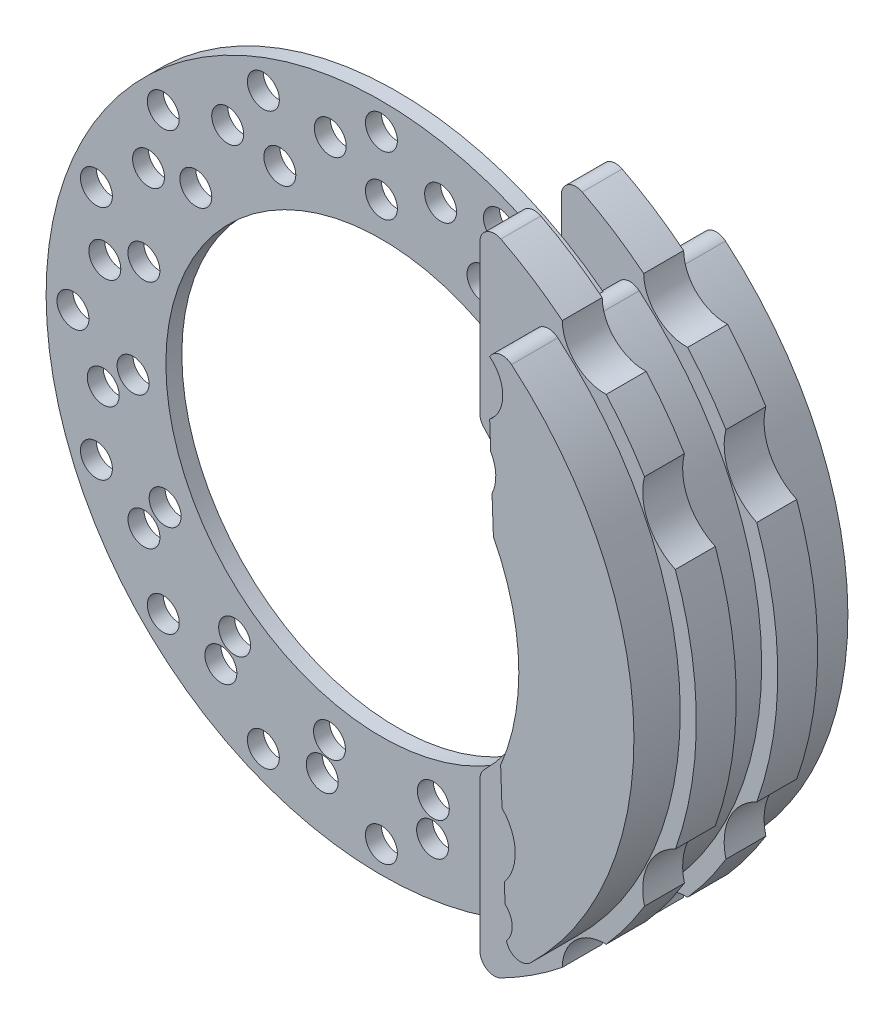
SolidWorks part; units mm, degrees
ref_plane "Front Plane" through (0, 0, 0) normal (0, 0, 1) x (1, 0, 0)
ref_plane "Top Plane" through (0, 0, 0) normal (0, 1, 0) x (1, 0, 0)
ref_plane "Right Plane" through (0, 0, 0) normal (1, 0, 0) x (0, 0, -1)
sketch "Sketch2" plane through (0, 0, 0) normal (0, 0, 1) x (1, 0, 0)
  circle A0 centre (0, 0) radius 210
  circle A1 centre (0, 0) radius 135
  dimension "D1" = 420
  dimension "D2" = 270
extrude "Boss-Extrude1" add sketch "Sketch2" along normal blind 10
sketch "Sketch3" plane through (0, 0, 0) normal (0, 0, 1) x (1, 0, 0)
  circle A0 centre (0, 0) radius 156.4104 construction
  circle A1 centre (0, 0) radius 177.149 construction
  circle A2 centre (0, 0) radius 193.1972 construction
  circle A3 centre (0, 193.1972) radius 10
  circle A17 centre (37.0719, 173.2265) radius 10
  circle A18 centre (100.5409, 145.8537) radius 10
  circle A19 centre (148.7034, 96.2759) radius 10
  circle A20 centre (174.2272, 32.041) radius 10
  circle A21 centre (173.2265, -37.0719) radius 10
  circle A22 centre (145.8537, -100.5409) radius 10
  circle A23 centre (96.2759, -148.7034) radius 10
  circle A24 centre (32.041, -174.2272) radius 10
  circle A25 centre (-37.0719, -173.2265) radius 10
  circle A26 centre (-100.5409, -145.8537) radius 10
  circle A27 centre (-148.7034, -96.2759) radius 10
  circle A28 centre (-174.2272, -32.041) radius 10
  circle A29 centre (-173.2265, 37.0719) radius 10
  circle A30 centre (-145.8537, 100.5409) radius 10
  circle A31 centre (-96.2759, 148.7034) radius 10
  circle A32 centre (-32.041, 174.2272) radius 10
  circle A33 centre (73.9334, 178.4909) radius 10
  circle A34 centre (136.611, 136.611) radius 10
  circle A35 centre (178.4909, 73.9334) radius 10
  circle A36 centre (193.1972, 0) radius 10
  circle A37 centre (178.4909, -73.9334) radius 10
  circle A38 centre (136.611, -136.611) radius 10
  circle A39 centre (73.9334, -178.4909) radius 10
  circle A40 centre (0, -193.1972) radius 10
  circle A41 centre (-73.9334, -178.4909) radius 10
  circle A42 centre (-136.611, -136.611) radius 10
  circle A43 centre (-178.4909, -73.9334) radius 10
  circle A44 centre (-193.1972, 0) radius 10
  circle A45 centre (-178.4909, 73.9334) radius 10
  circle A46 centre (-136.611, 136.611) radius 10
  circle A47 centre (-73.9334, 178.4909) radius 10
  circle A48 centre (0, 156.4104) radius 10
  circle A49 centre (63.6179, 142.888) radius 10
  circle A50 centre (116.2356, 104.659) radius 10
  circle A51 centre (148.7552, 48.3335) radius 10
  circle A52 centre (155.5536, -16.3493) radius 10
  circle A53 centre (135.4554, -78.2052) radius 10
  circle A54 centre (91.9357, -126.5387) radius 10
  circle A55 centre (32.5196, -152.9925) radius 10
  circle A56 centre (-32.5196, -152.9925) radius 10
  circle A57 centre (-91.9357, -126.5387) radius 10
  circle A58 centre (-135.4554, -78.2052) radius 10
  circle A59 centre (-155.5536, -16.3493) radius 10
  circle A60 centre (-148.7552, 48.3335) radius 10
  circle A61 centre (-116.2356, 104.659) radius 10
  circle A62 centre (-63.6179, 142.888) radius 10
  dimension "D1" = 20
  dimension "D3" = 20
  dimension "D2" = 20
  dimension "D4" = 16
  dimension "D5" = 16
  dimension "D6" = 15
extrude "Cut-Extrude1" cut sketch "Sketch3" against normal blind 10 and the other way blind 10
ref_plane "Plane1" through (0, 0, 13) normal (0, 0, 1) x (1, 0, 0)
sketch "Sketch4" plane through (0, 0, 13) normal (0, 0, 1) x (1, 0, 0)
  line L1 (89.6994, 192.3855) -> (89.6994, 99.0437)
  line L2 (89.6994, -99.0437) -> (89.6994, -192.3855)
  line L3 (0, 0) -> (377.9961, 0) construction
  arc A0 (102.8076, -200.3932) -> (141.2687, -175.4138) centre (0, 0) ccw
  arc A1 (92.3466, -92.6687) -> (92.3466, 92.6687) centre (0, 0) ccw
  arc A2 (92.3466, 92.6687) -> (89.6994, 99.0437) centre (98.6994, 99.0437) cw
  arc A3 (92.3466, -92.6687) -> (89.6994, -99.0437) centre (98.6994, -99.0437) ccw
  arc A4 (89.6994, -192.3855) -> (102.8076, -200.3932) centre (98.6994, -192.3855) ccw
  arc A5 (89.6994, 192.3855) -> (102.8076, 200.3932) centre (98.6994, 192.3855) cw
  arc A6 (168.7812, -149.13) -> (141.2687, -175.4138) centre (167.9372, -175.7878) ccw
  arc A7 (168.7812, -149.13) -> (192.7736, -116.4697) centre (0, 0) ccw
  arc A8 (212.0836, -75.8117) -> (192.7736, -116.4697) centre (226.725, -107.6799) ccw
  arc A9 (212.0836, -75.8117) -> (212.0836, 75.8117) centre (0, 0) ccw
  arc A10 (212.0836, 75.8117) -> (192.7736, 116.4697) centre (226.725, 107.6799) cw
  arc A11 (168.7812, 149.13) -> (141.2687, 175.4138) centre (167.9372, 175.7878) cw
  arc A12 (192.7736, 116.4697) -> (168.7812, 149.13) centre (0, 0) ccw
  arc A13 (141.2687, 175.4138) -> (102.8076, 200.3932) centre (0, 0) ccw
  dimension "D1" = 9
extrude "Boss-Extrude2" add sketch "Sketch4" along normal blind 25 separate body
ref_plane "Plane2" through (0, 0, -13) normal (0, 0, -1) x (-1, 0, 0)
sketch "Sketch6" plane through (0, 0, -13) normal (0, 0, -1) x (-1, 0, 0)
  line L0 (-89.6994, -99.0437) -> (-89.6994, -192.3855) construction
  line L1 (-89.6994, 192.3855) -> (-89.6994, 99.0437) construction
  line L2 (-89.6994, -99.0437) -> (-89.6994, -192.3855)
  line L3 (-89.6994, 192.3855) -> (-89.6994, 99.0437)
  arc A0 (-89.6994, -99.0437) -> (-92.3466, -92.6687) centre (-98.6994, -99.0437) ccw construction
  arc A1 (-92.3466, 92.6687) -> (-89.6994, 99.0437) centre (-98.6994, 99.0437) ccw construction
  arc A2 (-92.3466, 92.6687) -> (-92.3466, -92.6687) centre (0, 0) ccw construction
  arc A3 (-102.8076, -200.3932) -> (-89.6994, -192.3855) centre (-98.6994, -192.3855) ccw construction
  arc A4 (-141.2687, -175.4138) -> (-102.8076, -200.3932) centre (0, 0) ccw construction
  arc A5 (-141.2687, -175.4138) -> (-168.7812, -149.13) centre (-167.9372, -175.7878) ccw construction
  arc A6 (-192.7736, -116.4697) -> (-168.7812, -149.13) centre (0, 0) ccw construction
  arc A7 (-192.7736, -116.4697) -> (-212.0836, -75.8117) centre (-226.725, -107.6799) ccw construction
  arc A8 (-212.0836, 75.8117) -> (-212.0836, -75.8117) centre (0, 0) ccw construction
  arc A9 (-212.0836, 75.8117) -> (-192.7736, 116.4697) centre (-226.725, 107.6799) ccw construction
  arc A10 (-168.7812, 149.13) -> (-192.7736, 116.4697) centre (0, 0) ccw construction
  arc A11 (-168.7812, 149.13) -> (-141.2687, 175.4138) centre (-167.9372, 175.7878) ccw construction
  arc A12 (-102.8076, 200.3932) -> (-141.2687, 175.4138) centre (0, 0) ccw construction
  arc A13 (-89.6994, 192.3855) -> (-102.8076, 200.3932) centre (-98.6994, 192.3855) ccw construction
  arc A14 (-89.6994, -99.0437) -> (-92.3466, -92.6687) centre (-98.6994, -99.0437) ccw
  arc A15 (-92.3466, 92.6687) -> (-89.6994, 99.0437) centre (-98.6994, 99.0437) ccw
  arc A16 (-92.3466, 92.6687) -> (-92.3466, -92.6687) centre (0, 0) ccw
  arc A17 (-102.8076, -200.3932) -> (-89.6994, -192.3855) centre (-98.6994, -192.3855) ccw
  arc A18 (-141.2687, -175.4138) -> (-102.8076, -200.3932) centre (0, 0) ccw
  arc A19 (-141.2687, -175.4138) -> (-168.7812, -149.13) centre (-167.9372, -175.7878) ccw
  arc A20 (-192.7736, -116.4697) -> (-168.7812, -149.13) centre (0, 0) ccw
  arc A21 (-192.7736, -116.4697) -> (-212.0836, -75.8117) centre (-226.725, -107.6799) ccw
  arc A22 (-212.0836, 75.8117) -> (-212.0836, -75.8117) centre (0, 0) ccw
  arc A23 (-212.0836, 75.8117) -> (-192.7736, 116.4697) centre (-226.725, 107.6799) ccw
  arc A24 (-168.7812, 149.13) -> (-192.7736, 116.4697) centre (0, 0) ccw
  arc A25 (-168.7812, 149.13) -> (-141.2687, 175.4138) centre (-167.9372, 175.7878) ccw
  arc A26 (-102.8076, 200.3932) -> (-141.2687, 175.4138) centre (0, 0) ccw
  arc A27 (-89.6994, 192.3855) -> (-102.8076, 200.3932) centre (-98.6994, 192.3855) ccw
extrude "Boss-Extrude3" add sketch "Sketch6" along normal blind 25 separate body
sketch "Sketch7" plane through (0, 0, 0) normal (0, 0, 1) x (1, 0, 0)
  line L0 (124.7976, 128.1734) -> (125.442, 110.9191)
  line L1 (131.6737, -55.933) -> (132.5286, -78.8211)
  line L2 (126.2708, 88.7278) -> (127.1346, 65.5992)
  line L3 (0, 0) -> (111.3489, 0) construction
  line L4 (133.9975, -118.1521) -> (134.4404, -130.0106)
  arc A0 (150.3881, -153.8667) -> (138.4917, 164.656) centre (0, 0) ccw
  arc A1 (150.3881, -153.8667) -> (135.3218, -149.428) centre (144.0973, -147.4304) cw
  arc A2 (138.4917, 164.656) -> (124.8077, 162.0969) centre (132.6985, 157.7684) ccw
  arc A3 (131.6737, -55.933) -> (127.1346, 65.5992) centre (0, 0) ccw
  arc A4 (124.7976, 128.1734) -> (124.8077, 162.0969) centre (111.3489, 145.1392) ccw
  arc A5 (126.2708, 88.7278) -> (125.442, 110.9191) centre (104.9792, 99.0437) ccw
  arc A6 (133.9975, -118.1521) -> (132.5286, -78.8211) centre (111.3489, -99.305) ccw
  arc A8 (134.4404, -130.0106) -> (135.3218, -149.428) centre (125.1724, -140.16) cw
  dimension "D1" = 9
extrude "Boss-Extrude4" add sketch "Sketch7" along normal blind 67 and the other way blind 67
ref_plane "Plane3" through (0, 0, 5) normal (0, 0, 1) x (1, 0, 0)
sketch "Sketch8" plane through (0, 0, 5) normal (0, 0, 1) x (1, 0, 0)
  line L1 (-24.5607, 132.747) -> (-43.5498, 94.0673)
  line L2 (24.5607, 132.747) -> (43.5498, 94.0673)
  line L3 (132.747, 24.5607) -> (94.0673, 43.5498)
  line L4 (132.747, -24.5607) -> (94.0673, -43.5498)
  line L5 (24.5607, -132.747) -> (43.5498, -94.0673)
  line L6 (-24.5607, -132.747) -> (-43.5498, -94.0673)
  line L7 (-132.747, -24.5607) -> (-94.0673, -43.5498)
  line L8 (-132.747, 24.5607) -> (-94.0673, 43.5498)
  arc A0 (-94.0673, -43.5498) -> (-43.5498, -94.0673) centre (0, 0) ccw
  circle A1 centre (0, 0) radius 135 construction
  arc A2 (-43.5498, 94.0673) -> (-94.0673, 43.5498) centre (0, 0) ccw
  arc A3 (94.0673, 43.5498) -> (43.5498, 94.0673) centre (0, 0) ccw
  arc A4 (43.5498, -94.0673) -> (94.0673, -43.5498) centre (0, 0) ccw
  circle A5 centre (0, 0) radius 64.4678
  arc A6 (-24.5607, 132.747) -> (24.5607, 132.747) centre (0, -89.6672) cw
  arc A7 (-132.747, -24.5607) -> (-132.747, 24.5607) centre (104.5332, 0) cw
  arc A8 (132.747, 24.5607) -> (132.747, -24.5607) centre (-157.1058, 0) cw
  arc A9 (-24.5607, -132.747) -> (24.5607, -132.747) centre (0, -5.1185) ccw
  point P25 (0, 0)
  dimension "D1" = 4
